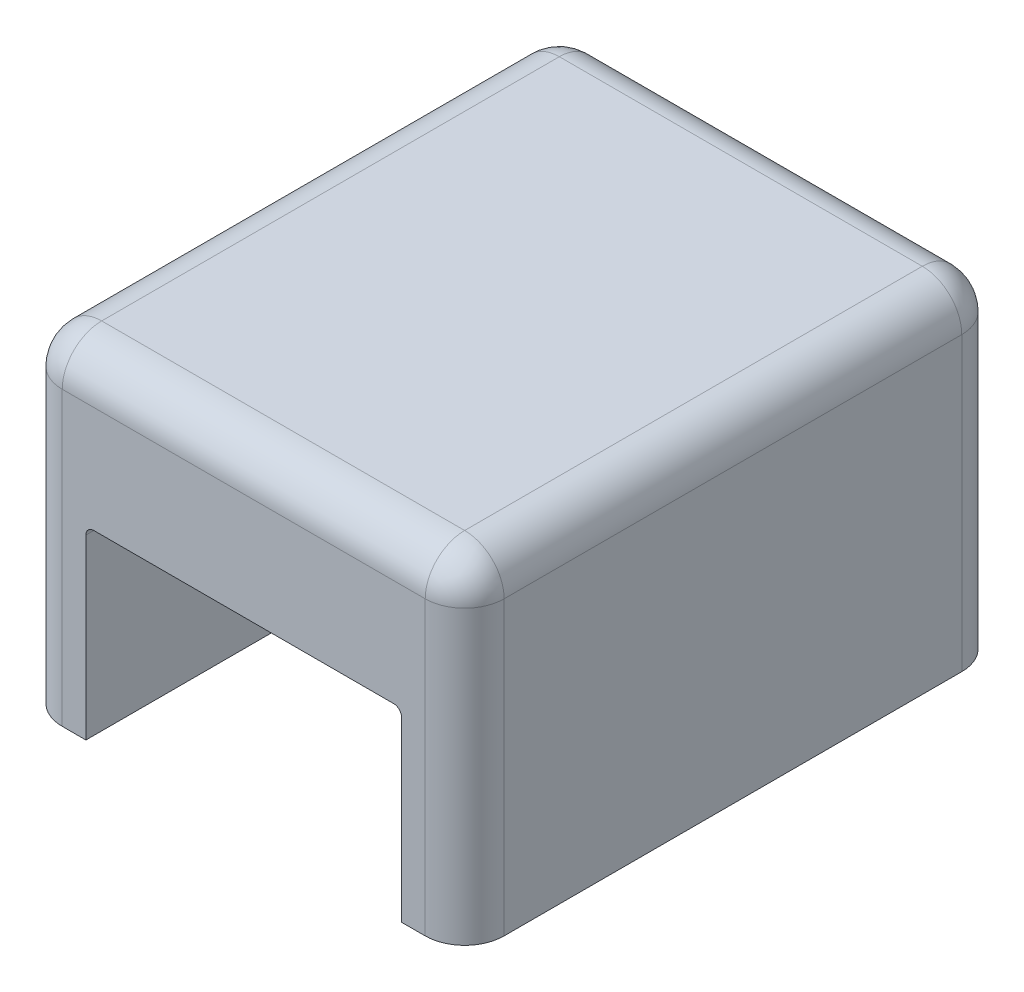
SolidWorks part; units mm, degrees
ref_plane "Front Plane" through (0, 0, 0) normal (0, 0, 1) x (1, 0, 0)
ref_plane "Top Plane" through (0, 0, 0) normal (0, 1, 0) x (1, 0, 0)
ref_plane "Right Plane" through (0, 0, 0) normal (1, 0, 0) x (0, 0, -1)
sketch "Sketch1" plane through (0, 0, 0) normal (1, 0, 0) x (0, 0, -1)
  line L1 (0, 0) -> (680, 0)
  line L2 (0, 0) -> (0, 420)
  line L3 (0, 420) -> (680, 420)
  line L4 (680, 0) -> (680, 420)
  dimension "D1" = 420
  dimension "D2" = 680
extrude "Boss-Extrude1" add sketch "Sketch1" along normal blind 560
sketch "Sketch4" plane through (0, 0, 0) normal (0, 0, 1) x (1, 0, 0)
  line L0 (560, 0) -> (0, 0) construction
  line L1 (80, 0) -> (480, 0)
  line L2 (80, 0) -> (80, 340)
  line L3 (80, 340) -> (480, 340)
  line L4 (480, 0) -> (480, 340)
  line L5 (560, 420) -> (560, 0) construction
  line L6 (560, 420) -> (0, 420) construction
  line L7 (0, 420) -> (0, 0) construction
  dimension "D1" = 80
  dimension "D2" = 80
  dimension "D3" = 80
extrude "Cut-Extrude1" cut sketch "Sketch4" against normal offset from surface (560 mm away) 120 up to face at (280, 210, -680)
ref_plane "Plane1" through (80, 0, 0) normal (1, 0, 0) x (0, 0, -1)
sketch "Sketch6" plane through (80, 0, 0) normal (1, 0, 0) x (0, 0, -1)
  line L1 (580, 80) -> (560, 80)
  line L2 (560, 80) -> (560, 160)
  line L3 (680, 0) -> (680, 420) construction
  line L4 (0, 0) -> (680, 0) construction
  line L5 (560, 160) -> (580, 160)
  line L6 (580, 160) -> (580, 80)
  dimension "D1" = 80
  dimension "D2" = 120
  dimension "D3" = 100
  dimension "D4" = 80
extrude "Cut-Extrude2" cut sketch "Sketch6" along normal up to surface (400 mm away) up to face at (480, 170, -280)
sketch "Sketch7" plane through (0, 0, -560) normal (0, 0, 1) x (1, 0, 0)
  line L3 (80, 160) -> (80, 340) construction
  line L5 (480, 160) -> (80, 160) construction
  circle A0 centre (105.125, 180.125) radius 15.125
  point P7 (280, 340)
  dimension "D1" = 30.25
  dimension "D2" = 5
  dimension "D3" = 10
extrude "Boss-Extrude2" add sketch "Sketch7" along normal offset from surface (410 mm away) 150 up to face at (280, 190, 0)
ref_plane "Plane2" through (0, 195.25, 0) normal (0, 1, 0) x (1, 0, 0)
ref_plane "Plane3" through (0, 0, -154) normal (0, 0, 1) x (1, 0, 0)
sketch "Sketch10" plane through (0, 0, -150) normal (0, 0, 1) x (1, 0, 0)
  circle A0 centre (105.125, 180.125) radius 11.125
  circle A1 centre (105.125, 180.125) radius 15.125 construction
  dimension "D1" = 4
extrude "Cut-Extrude3" cut sketch "Sketch10" against normal up to surface (410 mm away) from surface up to face at (120.25, 180.125, -560) starting at plane "Plane3"
sketch "Sketch9" plane through (0, 195.25, 0) normal (0, 1, 0) x (1, 0, 0)
  line L0 (90, 530) -> (120.25, 530) construction
  line L1 (90, 560) -> (90, 150) construction
  line L2 (120.25, 150) -> (120.25, 560) construction
  line L3 (80, 560) -> (480, 560) construction
  circle A0 centre (105.125, 530) radius 2.5
  circle A10 centre (105.125, 480) radius 2.5
  circle A11 centre (105.125, 430) radius 2.5
  circle A12 centre (105.125, 380) radius 2.5
  circle A13 centre (105.125, 330) radius 2.5
  circle A14 centre (105.125, 280) radius 2.5
  circle A15 centre (105.125, 230) radius 2.5
  circle A16 centre (105.125, 180) radius 2.5
  point P10 (105.125, 530)
  dimension "D1" = 5
  dimension "D2" = 30
  dimension "D3" = 8
extrude "Cut-Extrude4" cut sketch "Sketch9" against normal up to next
ref_axis "Axis1" through (280, 340, -560) along (0, -1, 0)
ref_plane "Plane4" through (280, 0, 0) normal (1, 0, 0) x (0, 0, -1)
sketch "Sketch11" plane through (80, 0, 0) normal (1, 0, 0) x (0, 0, -1)
  line L0 (150, 195.25) -> (150, 165) construction
  circle A0 centre (170, 179) radius 5
  dimension "D2" = 10
  dimension "D1" = 20
  dimension "D3" = 19
extrude "Boss-Extrude3" add sketch "Sketch11" along normal up to next
mirror "Mirror1" about plane through (280, 0, 0) normal (1, 0, 0) of "Boss-Extrude3", "Cut-Extrude3", "Cut-Extrude4", "Boss-Extrude2"
fillet "Fillet2" radius 50 8 edges at (280, 420, -680) (560, 420, -340) (280, 420, 0) (0, 420, -340) (0, 210, 0) (560, 210, 0) (560, 210, -680) (0, 210, -680)
sketch "Sketch13" plane through (0, 340, 0) normal (0, -1, 0) x (1, 0, 0)
  line L0 (480, -560) -> (480, 0) construction
  line L1 (80, 0) -> (480, 0)
  line L2 (80, 0) -> (80, -80)
  line L3 (80, -80) -> (480, -80)
  line L4 (480, 0) -> (480, -80)
  dimension "D1" = 80
extrude "Boss-Extrude4" add sketch "Sketch13" along normal blind 105
fillet "Fillet3" radius 5 20 edges at (480, 40, -560) (80, 40, -560) (480, 80, -570) (80, 80, -570) (280, 80, -560) (480, 340, -320) (480, 250, -560) (280, 340, -560) (80, 250, -560) (80, 340, -320) (80, 160, -570) (280, 160, -560) (480, 160, -570) (280, 80, -580) (80, 120, -580) (280, 160, -580) (480, 120, -580) (280, 340, -80) (480, 287.5, -80) (80, 287.5, -80)
fillet "Fillet4" radius 10 2 edges at (80, 235, -42.5) (480, 235, -42.5)
